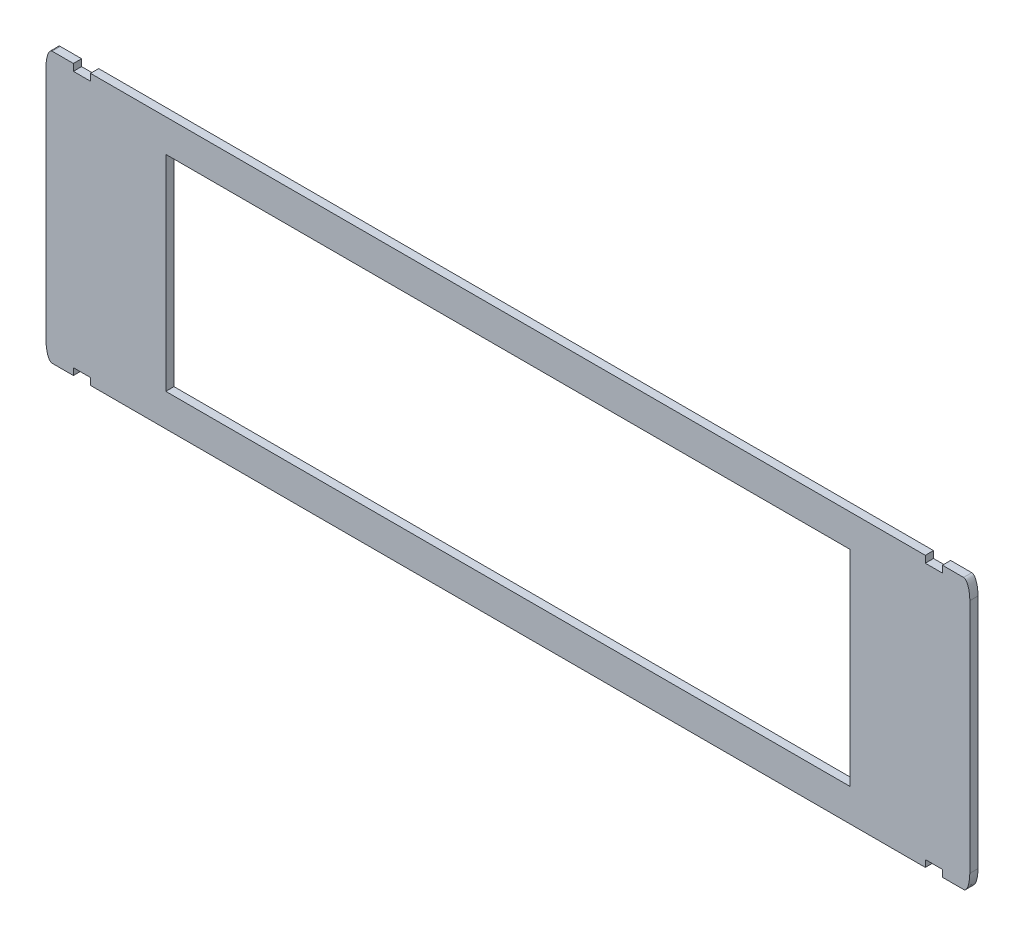
SolidWorks part; units mm, degrees
ref_plane "前视基准面" through (0, 0, 0) normal (0, 0, 1) x (1, 0, 0)
ref_plane "上视基准面" through (0, 0, 0) normal (0, 1, 0) x (1, 0, 0)
ref_plane "右视基准面" through (0, 0, 0) normal (1, 0, 0) x (0, 0, -1)
sketch "草图1" plane through (0, 0, 0) normal (0, 0, 1) x (1, 0, 0)
  line L1 (-135, 39.5) -> (135, 39.5)
  line L2 (-135, 39.5) -> (-135, -39.5)
  line L3 (-135, -39.5) -> (135, -39.5)
  line L4 (135, 39.5) -> (135, -39.5)
  line L5 (-135, 39.5) -> (135, -39.5) construction
  line L6 (-135, -39.5) -> (135, 39.5) construction
  point P0 (0, 0)
  dimension "D1" = 79
  dimension "D2" = 270
extrude "凸台-拉伸1" add sketch "草图1" along normal blind 2.4
sketch "草图2" plane through (0, 0, 2.4) normal (0, 0, 1) x (1, 0, 0)
  line L1 (-100, 30) -> (100, 30)
  line L2 (-100, 30) -> (-100, -30)
  line L3 (-100, -30) -> (100, -30)
  line L4 (100, 30) -> (100, -30)
  line L5 (-100, 30) -> (100, -30) construction
  line L6 (-100, -30) -> (100, 30) construction
  point P0 (0, 0)
  dimension "D1" = 200
  dimension "D2" = 60
extrude "切除-拉伸1" cut sketch "草图2" against normal through all
fillet "圆角1" radius 1.8 4 edges at (135, -39.5, 1.2) (135, 39.5, 1.2) (-135, -39.5, 1.2) (-135, 39.5, 1.2) second distance 5 first distance on face at (0, -39.5, 1.2) first distance on face at (0, 39.5, 1.2)
sketch "草图3" plane through (0, 0, 2.4) normal (0, 0, 1) x (1, 0, 0)
  line L0 (133.2, 39.5) -> (-133.2, 39.5) construction
  line L1 (-127, 39.5) -> (-122, 39.5)
  line L2 (-127, 39.5) -> (-127, 37.5)
  line L3 (-127, 37.5) -> (-122, 37.5)
  line L4 (-122, 39.5) -> (-122, 37.5)
  line L5 (-135, 34.5) -> (-135, -34.5) construction
  point P6 (-127, 38.5)
  dimension "D1" = 2
  dimension "D2" = 5
  dimension "D3" = 8
extrude "切除-拉伸2" cut sketch "草图3" against normal through all
mirror "镜向1" about plane through (0, 0, 0) normal (0, 1, 0) of "切除-拉伸2"
mirror "镜向2" about plane through (0, 0, 0) normal (1, 0, 0) of "切除-拉伸2", "镜向1"
